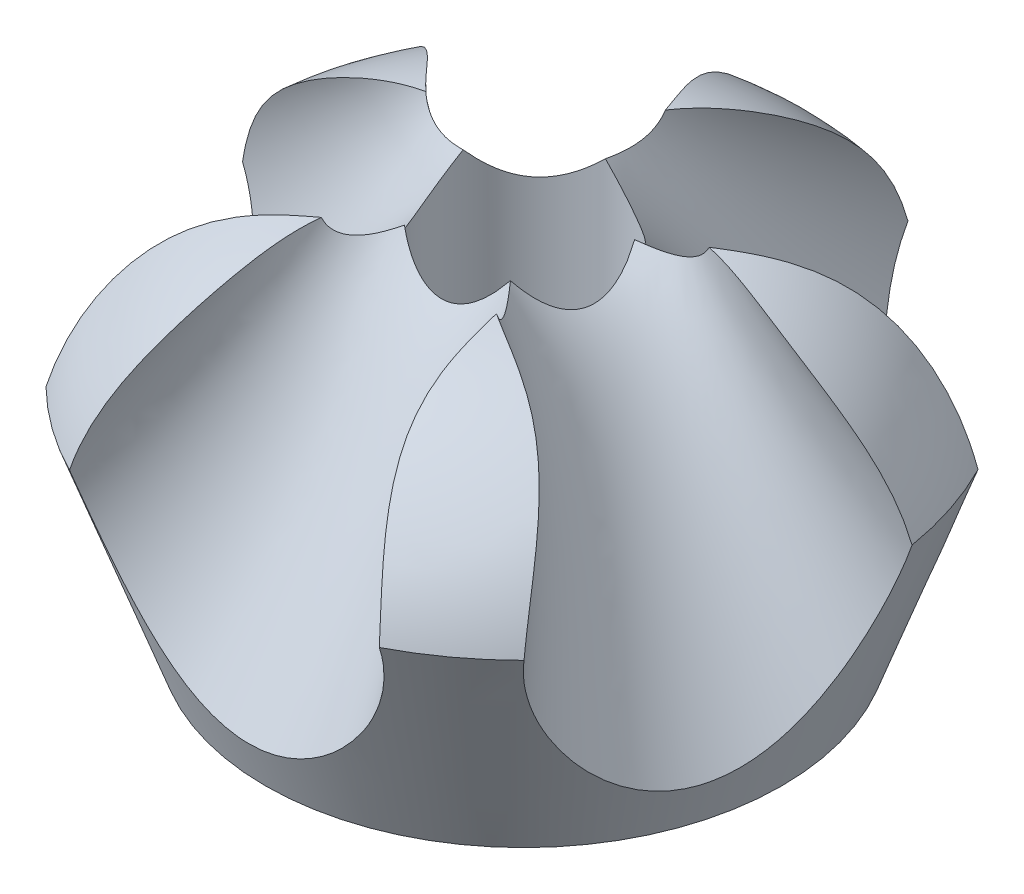
SolidWorks part; units mm, degrees
ref_plane "Front Plane" through (0, 0, 0) normal (0, 0, 1) x (1, 0, 0)
ref_plane "Top Plane" through (0, 0, 0) normal (0, 1, 0) x (1, 0, 0)
ref_plane "Right Plane" through (0, 0, 0) normal (1, 0, 0) x (0, 0, -1)
sketch "Sketch1" plane through (0, 0, 0) normal (0, 0, 1) x (1, 0, 0)
  line L0 (0, 0) -> (-15, 0)
  line L1 (-15, 0) -> (-19.6173, 12.6859)
  line L5 (0, 13) -> (0, 0)
  line L8 (0, 13) -> (0, 20.2524)
  arc A4 (-19.6173, 12.6859) -> (0, 20.2524) centre (-6.9751, 9.1227) cw
  point P8 (0, 27.7517)
  dimension "D1" = 15
  dimension "D2" = 13
  dimension "D3" = 13.5
  dimension "D6" = 110
revolve "Revolve1" add sketch "Sketch1" angle 360 about L5
ref_plane "Plane1" through (0, -4.8209, 13.2453) normal (0, -0.342, 0.9397) x (1, 0, 0)
sketch "Sketch4" plane through (0, -4.8209, 13.2453) normal (0, -0.342, 0.9397) x (1, 0, 0)
  circle A44 centre (0, 17.7606) radius 9.8847
  point P2 (0, 17.7606)
sketch3d "3DSketch1"
  point P4 (0, 27.7517, 0)
sketch "Sketch5" plane through (0, 0, 0) normal (0, 1, 0) x (1, 0, 0)
  circle A0 centre (0, 0) radius 5
  dimension "D1" = 10
extrude "Cut-Extrude1" cut sketch "Sketch5" along normal up to next
sketch "Sketch6" plane through (0, 0, 0) normal (0, 1, 0) x (1, 0, 0)
  line L0 (0, 7.435) -> (0, -7.1989) construction
sketch "Sketch9" plane through (0, 0, 0) normal (0, 0, 1) x (1, 0, 0)
  circle A2 centre (0, 29.5835) radius 6.4357
loft "Cut-Loft1" cut profiles "Sketch9", "Sketch4" connector at (6.377, 30.4502, 0) connector at (0, 2.5801, 15.9391)
pattern_circular "CirPattern1" count 5 over 360 about axis through (0, 12.6859, 0) along (0, -1, 0) of "Cut-Loft1"
